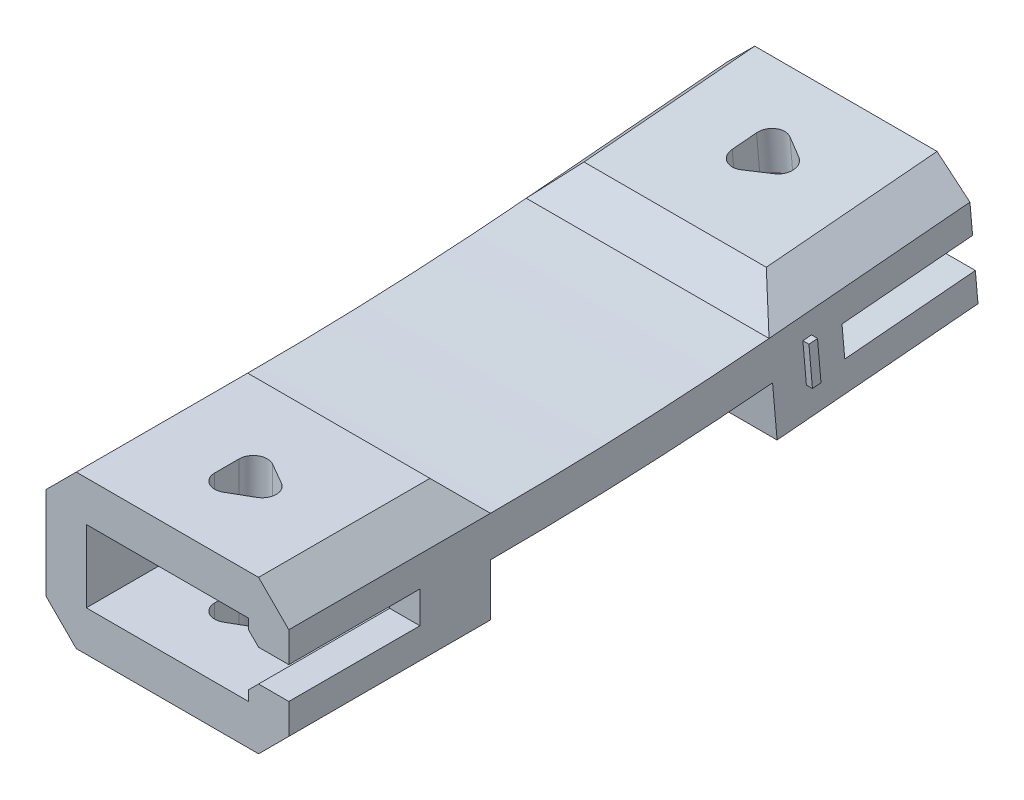
SolidWorks part; units mm, degrees
note: The reader was unsure of these and kept them because the rebuilt part matched: shared geometry of "Sketch1<2>", "Sketch5<4>".
ref_plane "Front Plane" through (0, 0, 0) normal (0, 0, 1) x (1, 0, 0)
ref_plane "Top Plane" through (0, 0, 0) normal (0, 1, 0) x (1, 0, 0)
ref_plane "Right Plane" through (0, 0, 0) normal (1, 0, 0) x (0, 0, -1)
other "Configuration Table"
sketch "Sketch1" plane through (0, 0, 0) normal (0, 0, 1) x (1, 0, 0)
  line L1 (4.02, -1.79) -> (-4.02, -1.79)
  line L2 (4.02, -1.79) -> (4.02, 1.79)
  line L3 (4.02, 1.79) -> (-4.02, 1.79)
  line L4 (-4.02, -1.79) -> (-4.02, 1.79)
  line L5 (0, 1.79) -> (0, -1.79) construction
  line L6 (4.02, 0) -> (-4.02, 0) construction
  line L7 (-6.02, 3.79) -> (6.02, 3.79)
  line L8 (-6.02, 3.79) -> (-6.02, -3.79)
  line L9 (-6.02, -3.79) -> (6.02, -3.79)
  line L10 (6.02, 3.79) -> (6.02, -3.79)
  line L11 (0, -3.79) -> (0, 3.79) construction
  line L12 (-6.02, 0) -> (6.02, 0) construction
  point P0 (0, 0)
  point P4 (0, 0)
  dimension "D1" = 3.58
  dimension "D2" = 8.04
  dimension "D3" = 2
  dimension "D4" = 2
extrude "Boss-Extrude1" add sketch "Sketch1" along normal blind 8
extrude "Boss-Extrude2" add sketch "Sketch1<2>" against normal blind 2 contours L4 L1 L2 L3 | L10 L7 L8 L9 L1 L4 L3 L2
sketch "Sketch1<2>" plane through (0, 0, 0) normal (0, 0, 1) x (1, 0, 0) same geometry as "Sketch1"
sketch "Sketch3" plane through (6.02, 9.81, 0) normal (1, 0, 0) x (0, -1, 0)
  line L0 (13.6, 2) -> (9.52, 2)
  line L2 (8.9093, 15.9867) -> (12.9738, 16.3423)
  line L3 (13.6, -8) -> (13.6, 2) construction
  arc A1 (9.52, 2) -> (8.9093, 15.9867) centre (-150.9591, 2) ccw
  arc A3 (12.9738, 16.3423) -> (13.6, 2) centre (-150.9591, 2) cw construction
  dimension "D1" = 4.08
  dimension "D4" = 5
  dimension "D2" = 14
extrude "Extrude-Thin1" add sketch "Sketch3" along normal up to surface (12.04 mm away) thin contours L0 A1 L2
sketch "Sketch5" plane through (0, -2.3561, -16.2716) normal (0, 0.0872, -0.9962) x (-1, 0, 0)
  line L1 (4.02, 1.1892) -> (-4.02, 1.1892)
  line L2 (4.02, 1.1892) -> (4.02, 4.7692)
  line L3 (4.02, 4.7692) -> (-4.02, 4.7692)
  line L4 (-4.02, 1.1892) -> (-4.02, 4.7692)
  line L5 (0, 4.7692) -> (0, 1.1892) construction
  line L6 (4.02, 2.9792) -> (-4.02, 2.9792) construction
  line L7 (-6.02, 6.7692) -> (6.02, 6.7692)
  line L8 (-6.02, 6.7692) -> (-6.02, -0.8108)
  line L9 (-6.02, -0.8108) -> (6.02, -0.8108)
  line L10 (6.02, 6.7692) -> (6.02, -0.8108)
  line L11 (0, -0.8108) -> (0, 6.7692) construction
  line L12 (-6.02, 2.9792) -> (6.02, 2.9792) construction
  line L13 (6.02, -0.8108) -> (-6.02, -0.8108) construction
  point P0 (0, 2.9792)
  point P4 (0, 2.9792)
  dimension "D1" = 3.58
  dimension "D2" = 8.04
  dimension "D3" = 2
  dimension "D4" = 2
extrude "Boss-Extrude4" add sketch "Sketch5" along normal blind 10
extrude "Boss-Extrude5" add sketch "Sketch5<4>" along normal blind 2 contours L8 L7 L10 L9
sketch "Sketch5<4>" plane through (0, -2.3561, -16.2716) normal (0, 0.0872, -0.9962) x (-1, 0, 0) same geometry as "Sketch5"
chamfer "Chamfer1" distance 1.5 angle 45 12 edges at (6.02, -2.728, -21.3232) (6.02, 4.8231, -20.6626) (-6.02, 4.8231, -20.6626) (-6.02, -2.728, -21.3232) (6.02, 3.79, 3) (6.02, -3.79, 3) (-6.02, -3.79, 3) (-6.02, 3.79, 3) (0, 3.79, -2) (0, -3.1638, -16.3423) (0, -3.79, -2) (0, 4.3874, -15.6816)
sketch "Sketch6" plane through (0, 3.79, 0) normal (0, 1, 0) x (1, 0, 0)
  line L0 (0, 2) -> (0, -8) construction
  line L4 (1.05, -3.3938) -> (0, -2.7876)
  line L5 (-1.05, -3.3938) -> (-1.05, -4.6062)
  line L6 (0, -5.2124) -> (1.05, -4.6062)
  line L7 (-6.02, 2) -> (6.02, 2) construction
  line L8 (4.52, -8) -> (-4.52, -8) construction
  line L9 (4.02, 0) -> (-4.02, 0) construction
  circle A0 centre (0, -4) radius 1.05 construction
  arc A1 (-1.05, -4.6062) -> (0, -5.2124) centre (-0.35, -4.6062) ccw
  arc A2 (0, -2.7876) -> (-1.05, -3.3938) centre (-0.35, -3.3938) ccw
  arc A3 (1.05, -3.3938) -> (1.05, -4.6062) centre (0.7, -4) cw
  point P15 (-1.05, -5.8187)
  point P18 (-1.05, -2.1813)
  dimension "D3" = 0.7
  dimension "D1" = 2.1
  dimension "D2" = 4
sketch "Sketch7" plane through (0, 2.9925, 0.2618) normal (0, 0.9962, 0.0872) x (1, 0, 0)
  line L0 (0, 26.0043) -> (0, 16.0043) construction
  line L4 (1.05, 22.6106) -> (0, 23.2168)
  line L5 (-1.05, 22.6106) -> (-1.05, 21.3981)
  line L6 (0, 20.7919) -> (1.05, 21.3981)
  line L7 (6.02, 16.0043) -> (-6.02, 16.0043) construction
  line L8 (4.52, 26.0043) -> (-4.52, 26.0043) construction
  line L9 (-4.02, 18.0043) -> (4.02, 18.0043) construction
  circle A0 centre (0, 22.0043) radius 1.05 construction
  arc A1 (-1.05, 21.3981) -> (0, 20.7919) centre (-0.35, 21.3981) ccw
  arc A2 (1.05, 22.6106) -> (1.05, 21.3981) centre (0.7, 22.0043) cw
  arc A3 (0, 23.2168) -> (-1.05, 22.6106) centre (-0.35, 22.6106) ccw
  dimension "D1" = 2.1
  dimension "D3" = 0.7
  dimension "D2" = 4
extrude "Cut-Extrude1" cut sketch "Sketch6" against normal through all both and the other way through all
extrude "Cut-Extrude2" cut sketch "Sketch7" against normal through all both and the other way through all
sketch "Sketch8" plane through (0, 2.2664, -25.9054) normal (0, 0.0872, -0.9962) x (-1, 0, 0)
  line L1 (-8.02, 0.0039) -> (-4.02, 0.0039)
  line L2 (-8.02, 0.0039) -> (-8.02, -1.5761)
  line L3 (-8.02, -1.5761) -> (-4.02, -1.5761)
  line L4 (-4.02, 0.0039) -> (-4.02, -1.5761)
  line L5 (-6.02, -1.5761) -> (-6.02, 0.0039) construction
  line L6 (-8.02, -0.7861) -> (-4.02, -0.7861) construction
  line L8 (-6.02, -3.0761) -> (-6.02, 1.5039) construction
  line L9 (-4.02, -2.5761) -> (-4.02, 1.0039) construction
  line L10 (4.02, -2.5761) -> (-4.02, -2.5761) construction
  point P0 (-6.02, -0.7861)
  dimension "D1" = 1.58
  dimension "D2" = 4
  dimension "D3" = 1
extrude "Cut-Extrude3" cut sketch "Sketch8" against normal offset from surface (6.5 mm away) 1.5 up to face at (0, 0.7861, -18.0043)
sketch "Sketch9" plane through (0, 0, 8) normal (0, 0, 1) x (1, 0, 0)
  line L1 (8.02, 0.79) -> (4.02, 0.79)
  line L2 (8.02, 0.79) -> (8.02, -0.79)
  line L3 (8.02, -0.79) -> (4.02, -0.79)
  line L4 (4.02, 0.79) -> (4.02, -0.79)
  line L5 (6.02, -0.79) -> (6.02, 0.79) construction
  line L6 (8.02, 0) -> (4.02, 0) construction
  line L8 (6.02, -2.29) -> (6.02, 2.29) construction
  line L9 (4.02, -1.79) -> (4.02, 1.79) construction
  line L10 (-4.02, -1.79) -> (4.02, -1.79) construction
  point P0 (6.02, 0)
  dimension "D1" = 1.58
  dimension "D2" = 4
  dimension "D3" = 1
extrude "Cut-Extrude4" cut sketch "Sketch9" against normal offset from surface (6.5 mm away) 1.5 up to face at (0, 0, 0)
chamfer "Chamfer2" distance 0.5 angle 45 6 edges at (4.02, 1.9871, -22.6674) (4.02, 0.9168, -19.4986) (4.02, 0.4131, -22.8051) (4.02, 0.79, 4.75) (4.02, 0, 1.5) (4.02, -0.79, 4.75)
sketch "Sketch10" [suppressed] plane through (6.02, 0, 0) normal (1, 0, 0) x (0, 0, -1)
  line L0 (22.5646, 0.2607) -> (19.0779, -0.0444) construction
  line L2 (18.9838, 1.0315) -> (19.2087, -1.5387) construction
  line L3 (22.5646, 0.2607) -> (22.4269, 1.8347) construction
  line L4 (29.0399, 0.8272) -> (22.5646, 0.2607) construction
  text T0 "<b>III</b>" font "@Microsoft YaHei" height 2
extrude "Boss-Extrude6" [suppressed] add sketch "Sketch10" along normal blind 0.3
sketch "Sketch11" [suppressed] plane through (6.02, 0, 0) normal (1, 0, 0) x (0, 0, -1)
  line L0 (21.5656, 0.2171) -> (18.0789, -0.088) construction
  line L1 (17.9848, 0.9879) -> (18.2096, -1.5823) construction
  line L2 (28.0408, 0.7836) -> (21.5656, 0.2171) construction
  text T0 "<b>II</b>\r\n" font "@Microsoft YaHei" height 2
extrude "Boss-Extrude7" [suppressed] add sketch "Sketch11" along normal blind 0.3
sketch "Sketch12" plane through (6.02, 0, 0) normal (1, 0, 0) x (0, 0, -1)
  line L0 (19.5675, 0.1298) -> (16.0808, -0.1752) construction
  line L1 (15.9867, 0.9007) -> (16.2115, -1.6695) construction
  line L2 (26.0428, 0.6963) -> (19.5675, 0.1298) construction
  text T0 "<b>I</b>\r\n" font "@Microsoft YaHei" height 2
extrude "Boss-Extrude8" add sketch "Sketch12" along normal blind 0.3
equation "\"LF\" = 0.04mm"
equation "\"TF\" = 0.02mm"
equation "\"AngLF\"= 0.5"
equation "\"AngTF\"= 0.3"
equation "\"D2@Sketch1\"=8+2*\"TF\""
equation "\"D1@Sketch1\"=3.5+2*\"LF\""
